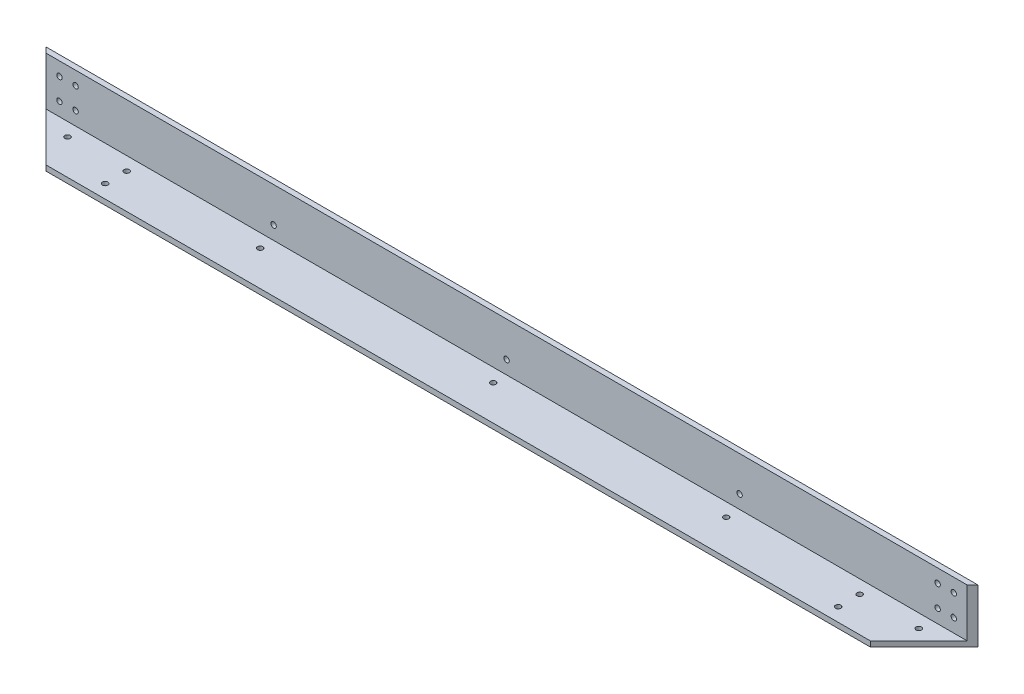
SolidWorks part; units mm, degrees
ref_plane "Front Plane" through (0, 0, 0) normal (0, 0, 1) x (1, 0, 0)
ref_plane "Top Plane" through (0, 0, 0) normal (0, 1, 0) x (1, 0, 0)
ref_plane "Right Plane" through (0, 0, 0) normal (1, 0, 0) x (0, 0, -1)
sketch "Sketch1" plane through (0, 0, 0) normal (1, 0, 0) x (0, 0, -1)
  line L0 (0, 0) -> (-31.75, 0)
  line L1 (-31.75, 0) -> (-31.75, 3.175)
  line L2 (-31.75, 3.175) -> (-3.175, 3.175)
  line L3 (-3.175, 3.175) -> (-3.175, 31.75)
  line L4 (-3.175, 31.75) -> (0, 31.75)
  line L5 (0, 31.75) -> (0, 0)
  dimension "LHeight" = 31.75
  dimension "LWidth" = 31.75
  dimension "LMaterialThickness" = 3.175
  dimension "D1" = 28.575
  dimension "D2" = 28.575
  dimension "D3" = 3.175
extrude "Boss-Extrude1" add sketch "Sketch1" along normal blind 550
chamfer "Chamfer6" distance 31.75 angle 45 1 edges at (550, 1.5875, 31.75)
chamfer "Chamfer7" distance 31.75 angle 45 1 edges at (0, 1.5875, 31.75)
sketch "TopHoles-Sketch3" plane through (0, 3.175, 0) normal (0, 1, 0) x (1, 0, 0)
  line L1 (518.25, -31.75) -> (31.75, -31.75) construction
  line L2 (550, 0) -> (0, 0) construction
  circle A5 centre (58.7375, -23.8125) radius 1.5875
  circle A6 centre (491.2625, -23.8125) radius 1.5875
  circle A9 centre (491.2625, -11.1125) radius 1.5875
  circle A10 centre (58.7375, -11.1125) radius 1.5875
  circle A11 centre (526.1875, -11.1125) radius 1.5875
  circle A12 centre (23.8125, -11.1125) radius 1.5875
  circle A13 centre (137.5, -11.1125) radius 1.5875
  circle A14 centre (275, -11.1125) radius 1.5875
  circle A15 centre (412.5, -11.1125) radius 1.5875
  dimension "D8" = 137.5
  dimension "D10" = 137.5
  dimension "D9" = 3.175
  dimension "D12" = 7.9375
  dimension "D2" = 11.1125
  dimension "D6" = 23.8125
  dimension "D3" = 23.8125
  dimension "D5" = 12.7
  dimension "D4" = 34.925
  dimension "D7" = 34.925
  dimension "D11" = 137.5
extrude "TopHoles-Cut-Extrude2" cut sketch "TopHoles-Sketch3" against normal through all
sketch "SideHoles-Sketch4" plane through (0, 0, 3.175) normal (0, 0, 1) x (1, 0, 0)
  line L0 (518.25, 0) -> (31.75, 0) construction
  line L3 (550, 31.75) -> (0, 31.75) construction
  line L4 (0, 0) -> (0, 31.75) construction
  line L5 (550, 0) -> (550, 31.75) construction
  circle A1 centre (11.1125, 23.8125) radius 1.5875
  circle A3 centre (529.3625, 23.8125) radius 1.5875
  circle A4 centre (20.6375, 23.8125) radius 1.5875
  circle A5 centre (538.8875, 23.8125) radius 1.5875
  circle A6 centre (11.1125, 11.1125) radius 1.5875
  circle A7 centre (20.6375, 11.1125) radius 1.5875
  circle A8 centre (529.3625, 11.1125) radius 1.5875
  circle A9 centre (538.8875, 11.1125) radius 1.5875
  circle A10 centre (137.5, 11.1125) radius 1.5875
  circle A11 centre (275, 11.1125) radius 1.5875
  circle A12 centre (412.5, 11.1125) radius 1.5875
  dimension "D2" = 3.175
  dimension "D4" = 7.9375
  dimension "D7" = 11.1125
  dimension "D1" = 11.1125
  dimension "D6" = 20.6375
  dimension "D3" = 11.1125
  dimension "D5" = 20.6375
  dimension "D8" = 137.5
  dimension "D9" = 137.5
  dimension "D10" = 137.5
extrude "SideHoles-Cut-Extrude3" cut sketch "SideHoles-Sketch4" against normal through all
equation "\"TopRailWidth\"= 1.25in"
equation "\"TopRailHeight\"= 1.25in"
equation "\"RailThickness\"= .125in'Spec"
equation "\"SideRailHoleY1FromEdge\"= \"HoleOffsetFromEdge\""
equation "\"SideRailHoleX1FromSide\"= \"HoleOffsetFromSide\""
equation "\"SideRailLength\"= 550mm"
equation "\"VSWidth\"= 1.25in'Spec"
equation "\"HoleOffsetFromEdge\"= \"RailThickness\" * 2.5"
equation "\"HoleOffsetFromSide\"= \"RailThickness\" * 3.5"
equation "\"TopHoleY1FromSide\"= \"HoleOffsetFromSide\""
equation "\"TopHoleX1FromEdge\"= \"TopCBWidth\" - \"HoleOffsetFromEdge\"'Equals 20.6375"
equation "\"TopCBWidth\"= \"TopRailWidth\" - \"RailThickness\"'Equals 28.575"
equation "\"SideRailHoleX2FromSide\"= \"VSWidth\" - \"HoleOffsetFromEdge\" - \"RailThickness\"'Equals 20.6375"
equation "\"FasteningHoleDiameter\"= .125in"
equation "\"SideRailHoleY2FromSide\"= \"HoleOffsetFromSide\""
equation "\"D2@SideHoles-Sketch4\"=\"FasteningHoleDiameter\""
equation "\"LWidth@Sketch1\"=\"TopRailWidth\""
equation "\"LHeight@Sketch1\"=\"TopRailHeight\""
equation "\"LMaterialThickness@Sketch1\"=\"RailThickness\""
equation "\"D1@Boss-Extrude1\"=\"SideRailLength\""
equation "\"D2@TopHoles-Sketch3\"=\"TopHoleY1FromSide\""
equation "\"D9@TopHoles-Sketch3\" = \"FasteningHoleDiameter\""
equation "\"D4@SideHoles-Sketch4\"=\"SideRailHoleY1FromEdge\""
equation "\"D1@Chamfer6\"=\"TopRailWidth\""
equation "\"D1@Chamfer7\"=\"TopRailWidth\""
equation "\"D7@SideHoles-Sketch4\"=\"SideRailHoleY2FromSide\""
equation "\"D1@SideHoles-Sketch4\"=\"SideRailHoleX1FromSide\""
equation "\"D6@SideHoles-Sketch4\"=\"SideRailHoleX2FromSide\""
equation "\"D3@SideHoles-Sketch4\"=\"SideRailHoleX1FromSide\""
equation "\"D5@SideHoles-Sketch4\"=\"SideRailHoleX2FromSide\""
equation "\"TopHoleX2FromX1\"= \"TopCBLength\" - \"TopHoleX1FromEdge\" - \"HoleOffsetFromEdge\"'Equals 34.925"
equation "\"TopHoleY2FromY1\"= \"TopCBWidth\" - \"TopHoleY1FromEdge\" - \"HoleOffsetFromEdge\"'Equals 12.7"
equation "\"D3@TopHoles-Sketch3\"=\"TopHoleX1FromEdge\" + \"RailThickness\""
equation "\"D6@TopHoles-Sketch3\"=\"TopHoleX1FromEdge\" + \"RailThickness\""
equation "\"D5@TopHoles-Sketch3\"=\"TopHoleY2FromY1\""
equation "\"TopCBLength\"= \"TopRailWidth\" * 2'Equals 63.5"
equation "\"TopHoleY1FromEdge\"= \"HoleOffsetFromEdge\""
equation "\"D4@TopHoles-Sketch3\"=\"TopHoleX2FromX1\""
equation "\"D7@TopHoles-Sketch3\"=\"TopHoleX2FromX1\""
equation "\"LeftOrRightEnclosureOffsets\"= \"SideRailLength\" / 4"
equation "\"D8@TopHoles-Sketch3\"=\"LeftOrRightEnclosureOffsets\""
equation "\"D10@TopHoles-Sketch3\"=\"LeftOrRightEnclosureOffsets\""
equation "\"D11@TopHoles-Sketch3\"=\"LeftOrRightEnclosureOffsets\""
equation "\"D8@SideHoles-Sketch4\"=\"LeftOrRightEnclosureOffsets\""
equation "\"D9@SideHoles-Sketch4\"=\"LeftOrRightEnclosureOffsets\""
equation "\"D10@SideHoles-Sketch4\"=\"LeftOrRightEnclosureOffsets\""
